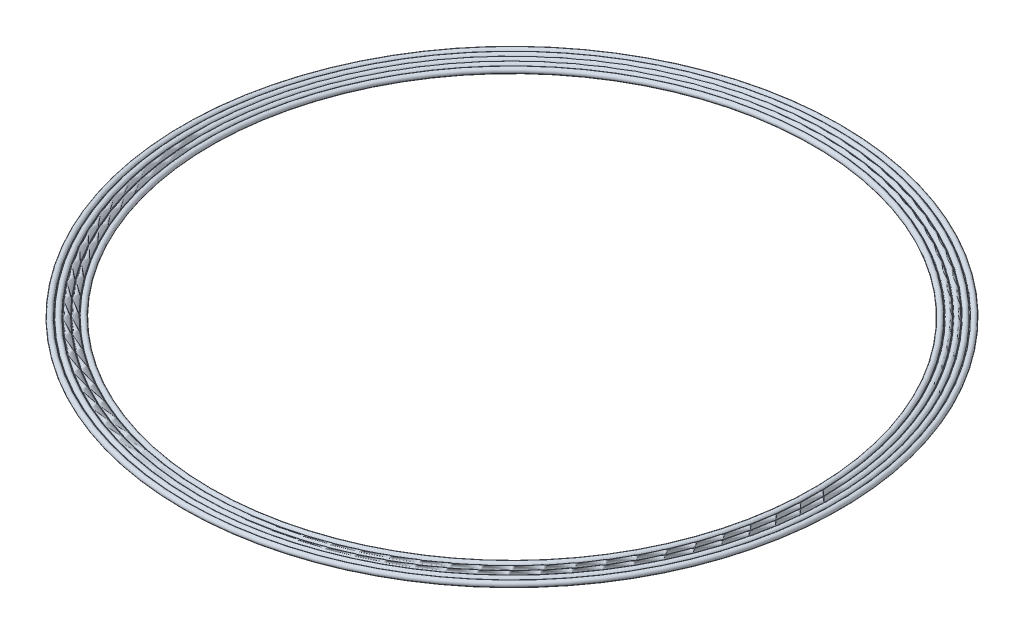
SolidWorks part; units mm, degrees
material "Copper"
ref_plane "Front Plane" through (0, 0, 0) normal (0, 0, 1) x (1, 0, 0)
ref_plane "Top Plane" through (0, 0, 0) normal (0, 1, 0) x (1, 0, 0)
ref_plane "Right Plane" through (0, 0, 0) normal (1, 0, 0) x (0, 0, -1)
sketch "Sketch2" plane through (0, 0, 0) normal (0, 0, 1) x (1, 0, 0)
  line L0 (0, 6.4506) -> (0, -5.0269) construction
  line L1 (0, 0) -> (101.75, 0) construction
  line L2 (94.3261, 0.2) -> (94.5239, 0.2)
  line L3 (94.3261, -0.2) -> (94.5239, -0.2)
  line L4 (96.1761, -0.2) -> (96.3739, -0.2)
  line L5 (96.1761, 0.2) -> (96.3739, 0.2)
  line L6 (98.0261, 0.2) -> (98.2239, 0.2)
  line L7 (98.0261, -0.2) -> (98.2239, -0.2)
  line L8 (99.8761, -0.2) -> (100.0739, -0.2)
  line L9 (99.8761, 0.2) -> (100.0739, 0.2)
  arc A0 (100.0739, -0.2) -> (100.0739, 0.2) centre (100.9, 0) ccw
  arc A1 (98.2239, -0.2) -> (99.8761, -0.2) centre (99.05, 0) ccw
  arc A2 (96.3739, -0.2) -> (98.0261, -0.2) centre (97.2, 0) ccw
  arc A3 (94.5239, -0.2) -> (96.1761, -0.2) centre (95.35, 0) ccw
  arc A4 (94.3261, 0.2) -> (94.3261, -0.2) centre (93.5, 0) ccw
  arc A5 (96.1761, 0.2) -> (94.5239, 0.2) centre (95.35, 0) ccw
  arc A6 (98.0261, 0.2) -> (96.3739, 0.2) centre (97.2, 0) ccw
  arc A7 (99.8761, 0.2) -> (98.2239, 0.2) centre (99.05, 0) ccw
  point P6 (94.425, -0.2)
  point P15 (92.65, 0)
  point P28 (0, 0)
  dimension "D1" = 1.7
  dimension "D3" = 9.1
  dimension "D4" = 1.85
  dimension "D5" = 1.85
  dimension "D6" = 1.85
  dimension "D7" = 0.2
  dimension "D8" = 0.2
  dimension "D2" = 203.5
revolve "Revolve1" add sketch "Sketch2" angle 360 about L0
ref_axis "Axis1" through (0, 6.4506, 0) along (0, -1, 0)
equation "\"D4@Sketch2\"=(\"D3@Sketch2\" -\"D1@Sketch2\")/4"
equation "\"D5@Sketch2\"=\"D4@Sketch2\""
equation "\"D6@Sketch2\"=\"D4@Sketch2\""
equation "\"ferrite_width\"= 12mm"
